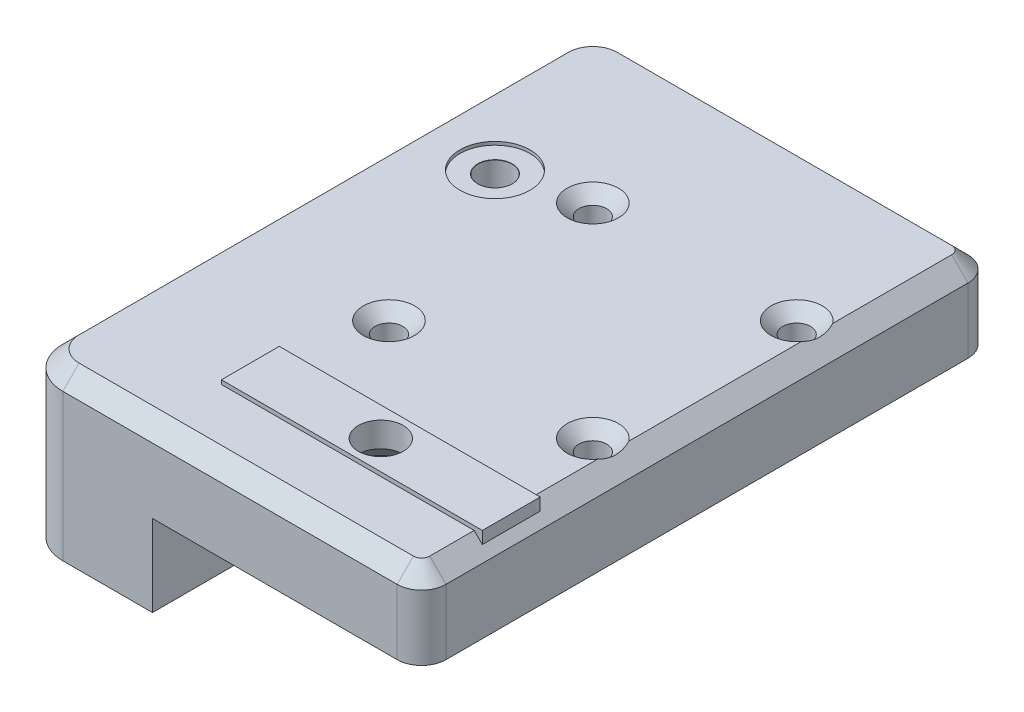
SolidWorks part; units mm, degrees
material "3.1355 (EN-AW 2024)"
ref_plane "Front" through (0, 0, 0) normal (0, 0, 1) x (1, 0, 0)
ref_plane "Top" through (0, 0, 0) normal (0, 1, 0) x (1, 0, 0)
ref_plane "Right" through (0, 0, 0) normal (1, 0, 0) x (0, 0, -1)
sketch "Эскиз1" plane through (0, 0, 0) normal (0, 1, 0) x (1, 0, 0)
  line L1 (-17, 35) -> (17, 35)
  line L2 (-17, 35) -> (-17, -35)
  line L3 (-17, -35) -> (17, -35)
  line L4 (17, 35) -> (17, -35)
  line L5 (-17, 35) -> (17, -35) construction
  line L6 (-17, -35) -> (17, 35) construction
  point P0 (0, 0)
  dimension "D1" = 70
  dimension "D2" = 34
extrude "База" add sketch "Эскиз1" against normal blind 10
sketch "Эскиз7" plane through (0, 0, 0) normal (0, -1, 0) x (-1, 0, 0)
  line L0 (17, 35) -> (17, -35) construction
  line L1 (17, 35) -> (32, 35)
  line L2 (17, 35) -> (17, -35)
  line L3 (17, -35) -> (32, -35)
  line L4 (32, 35) -> (32, -35)
  line L5 (17, 35) -> (17, -35) construction
  point P6 (17, 0)
  dimension "D2" = 15
extrude "База2" add sketch "Эскиз7" along normal up to surface (10 mm away) up to face at (0, -10, 0)
hole_wizard "Крепление каретки M3" positions "Эскиз2" profile "Эскиз3" countersink size "M3" standard "ISO" end condition through all
sketch "Эскиз2" plane through (0, 0, 0) normal (0, -1, 0) x (-1, 0, 0)
  line L0 (-12.5, 15.5) -> (0, 15.5) construction
  line L1 (0, 15.5) -> (12.5, 15.5) construction
  line L2 (12.5, 15.5) -> (12.5, 3) construction
  line L3 (12.5, 3) -> (12.5, -9.5) construction
  point P0 (-12.5, 15.5)
  point P2 (12.5, 15.5)
  point P4 (12.5, -9.5)
  point P6 (-12.5, -9.5)
  dimension "D1" = 25
  dimension "D2" = 25
  dimension "D3" = 3
sketch "Эскиз3" plane through (12.5, 0, -15.5) normal (1, 0, 0) x (0, 0, 1)
  line L0 (0, 0) -> (0, 10)
  line L1 (0, 10) -> (1.7, 10)
  line L2 (1.7, 10) -> (1.7, 1.45)
  line L3 (1.7, 1.45) -> (3.15, 0)
  line L5 (3.15, 0) -> (0, 0)
  line L6 (-1.7, 1.45) -> (-3.15, 0) construction
  line L11 (0, -6.35) -> (0, 107.95) construction
  dimension "Диаметр сквозного отверстия" = 3.4
  dimension "Глубина сквозного отверстия" = 10
  dimension "Диаметр передней зенковки" = 6.3
  dimension "Угол передней зенковки" = 90
sketch "Эскиз17" plane through (0, 0, 0) normal (0, 1, 0) x (1, 0, 0)
  line L7 (-16, -19.45) -> (16, -19.45)
  line L8 (-16, -19.45) -> (-16, -26.55)
  line L9 (-16, -26.55) -> (16, -26.55)
  line L10 (16, -19.45) -> (16, -26.55)
  line L11 (-16, -19.45) -> (16, -26.55) construction
  line L12 (-16, -26.55) -> (16, -19.45) construction
  point P6 (0, -23)
  dimension "D1" = 7.1
  dimension "D2" = 32
  dimension "D3" = 23
extrude "Направляющая" add sketch "Эскиз17" along normal blind 0.5
sketch "Эскиз19" plane through (0, -10, 0) normal (0, 1, 0) x (1, 0, 0)
  line L0 (12.5, -9.5) -> (-12.5, -9.5) construction
  line L1 (-16, -28) -> (16, -28)
  line L2 (-16, -28) -> (-16, 34)
  line L3 (-16, 34) -> (16, 34)
  line L4 (16, -28) -> (16, 34)
  line L5 (-12.5, -9.5) -> (-12.5, 15.5) construction
  point P14 (0, -28)
  point P15 (0, -9.5)
  point P16 (-12.5, 3)
  point P17 (-16, 3)
  dimension "D1" = 32
  dimension "D2" = 62
extrude "Вырез-Вытянуть2" cut sketch "Эскиз19" along normal blind 5
hole_wizard "НижнееКрепление-M5" positions "Эскиз15" profile "Эскиз16" countersink size "M5" standard "DIN"
sketch "Эскиз15" plane through (0, -5, 0) normal (0, -1, 0) x (-1, 0, 0)
  line L15 (0, -23) -> (0, -19.45) construction
  line L16 (-16, -19.45) -> (16, -19.45) construction
  line L19 (0, -23) -> (0, -26.55) construction
  line L20 (16, -26.55) -> (-16, -26.55) construction
  point P58 (0, -23)
sketch "Эскиз16" plane through (0, -5, 23) normal (1, 0, 0) x (0, 0, -1)
  line L0 (0, 0) -> (0, 23.1524)
  line L1 (0, 23.1524) -> (2.75, 21.5)
  line L2 (2.75, 21.5) -> (2.75, 2.45)
  line L3 (2.75, 2.45) -> (5.2, 0)
  line L5 (5.2, 0) -> (0, 0)
  line L6 (-2.75, 2.45) -> (-5.2, 0) construction
  line L10 (0, 23.1524) -> (-2.75, 21.5) construction
  line L11 (0, -6.35) -> (0, 107.95) construction
  dimension "Диаметр отверстия" = 5.5
  dimension "Глубина отверстия" = 21.5
  dimension "Диаметр передней зенковки" = 10.4
  dimension "Угол передней зенковки" = 90
  dimension "Угол заточки сверла" = 118
sketch "Эскиз21" plane through (0, -10, 0) normal (0, -1, 0) x (1, 0, 0)
  line L0 (17, -35) -> (-32, -35) construction
  line L1 (-32, 35) -> (-16, 35)
  line L2 (-32, 35) -> (-32, -35)
  line L3 (-32, -35) -> (-16, -35)
  line L4 (-16, 35) -> (-16, -35)
  line L5 (-16, -34) -> (-16, 28) construction
  line L6 (-32, -35) -> (-32, 35) construction
  line L7 (-32, 35) -> (17, 35) construction
extrude "Бобышка-Вытянуть1" add sketch "Эскиз21" along normal blind 10
hole_wizard "Шкивы-M5" positions "Эскиз4" profile "Эскиз5" tap size "M5" standard "ISO" end condition through all
sketch "Эскиз4" plane through (0, 0, 0) normal (0, -1, 0) x (-1, 0, 0)
  circle A0 centre (0, -23) radius 2.75 construction
  point P0 (22, 13)
  dimension "D1" = 22
  dimension "D2" = 36
sketch "Эскиз5" plane through (-22, 0, -13) normal (1, 0, 0) x (0, 0, 1)
  line L0 (0, 0) -> (0, 20)
  line L1 (0, 20) -> (2.1, 20)
  line L2 (2.1, 20) -> (2.1, 0.425)
  line L3 (2.1, 0.425) -> (2.525, 0)
  line L5 (2.525, 0) -> (0, 0)
  line L6 (-2.1, 0.425) -> (-2.525, 0) construction
  line L11 (0, -6.35) -> (0, 107.95) construction
  dimension "Диаметр проходного сверла" = 4.2
  dimension "Глубина проходного сверла" = 20
  dimension "Диаметр передней зенковки" = 5.05
  dimension "Угол передней зенковки" = 90
cosmetic thread "Отверстие резьбы2" parameters "D2"=5
fillet "Скругление1" radius 3 2 edges at (17, -5, -35) (17, -5, 35)
fillet "Скругление3" radius 5 2 edges at (-32, -10, -35) (-32, -10, 35)
sketch "Эскиз18" plane through (0, 0, 0) normal (0, 1, 0) x (1, 0, 0)
  circle A0 centre (-22, 13) radius 4.3
  dimension "D1" = 8.6
extrude "Вырез-Вытянуть1" cut sketch "Эскиз18" against normal blind 0.4
fillet "Скругление2" radius 2 4 edges at (-16, -7.5, 28) (16, -7.5, 28) (16, -7.5, -34) (-16, -7.5, -34)
chamfer "Фаска2" distance 2 angle 45 8 edges at (16.1213, 0, 34.1213) (17, 0, 0) (16.1213, 0, -34.1213) (-6.5, 0, -35) (-32, 0, 0) (-6.5, 0, 35) (-30.5355, 0, -33.5355) (-30.5355, 0, 33.5355)
